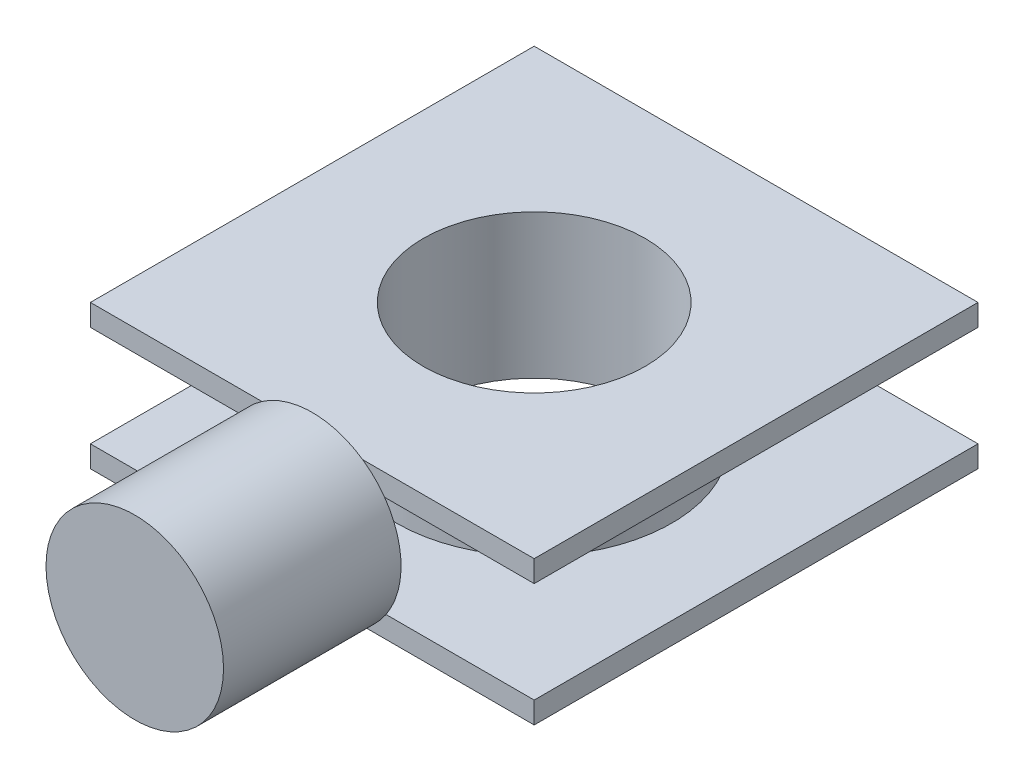
SolidWorks part; units mm, degrees
ref_plane "Front Plane" through (0, 0, 0) normal (0, 0, 1) x (1, 0, 0)
ref_plane "Top Plane" through (0, 0, 0) normal (0, 1, 0) x (1, 0, 0)
ref_plane "Right Plane" through (0, 0, 0) normal (1, 0, 0) x (0, 0, -1)
sketch "Sketch1" plane through (0, 0, 0) normal (0, 1, 0) x (1, 0, 0)
  line L1 (25, -25) -> (-25, -25)
  line L2 (25, -25) -> (25, 25)
  line L3 (25, 25) -> (-25, 25)
  line L4 (-25, -25) -> (-25, 25)
  line L5 (25, -25) -> (-25, 25) construction
  line L6 (25, 25) -> (-25, -25) construction
  circle A1 centre (0, 0) radius 12.5
  circle A2 centre (0, 0) radius 15.5
  circle A3 centre (0, 0) radius 100
  dimension "D2" = 25
  dimension "D3" = 3
  dimension "D4" = 200
  dimension "D5" = 50
  dimension "D6" = 50
extrude "Boss-Extrude1" add sketch "Sketch1" along normal blind 15 contours A2 A1 region at (-15.0616, 0, 0)
sketch "Sketch2" plane through (0, 0, 0) normal (0, 0, 1) x (1, 0, 0)
  line L0 (-15.5, 0) -> (15.5, 0) construction
  line L1 (-50, 2.4358) -> (50, 2.4358)
  line L2 (-50, 2.4358) -> (-50, -2.4358)
  line L3 (-50, -2.4358) -> (50, -2.4358)
  line L4 (50, 2.4358) -> (50, -2.4358)
  line L5 (-50, 2.4358) -> (50, -2.4358) construction
  line L6 (-50, -2.4358) -> (50, 2.4358) construction
  line L7 (-1000, 0) -> (49000, 0) construction
  line L8 (-50, 0) -> (50, 0)
  line L9 (0, -1000) -> (0, 49000) construction
  line L10 (-50, 18.6667) -> (50, 18.6667)
  line L11 (-50, 18.6667) -> (-50, 13.795)
  line L12 (-50, 13.795) -> (50, 13.795)
  line L13 (50, 18.6667) -> (50, 13.795)
  line L14 (-50, 18.6667) -> (50, 13.795) construction
  line L15 (-50, 13.795) -> (50, 18.6667) construction
  line L16 (-50, 16.2308) -> (50, 16.2308)
  point P0 (0, 0)
  point P12 (0, 16.2308)
  point P20 (0, 0)
  dimension "D1" = 100
  dimension "D2" = 100
extrude "Boss-Extrude2" add sketch "Sketch2" along normal blind 50 and the other way blind 50 contours L2 L8 L4 L1 | L16 L11 L12 L13 region at (0, 1.2179, 0) region at (0, 15.0129, 0)
extrude "Cut-Extrude1" cut sketch "Sketch1<4>" along normal blind 20 contours A1 region at (0, 0, 0)
sketch "Sketch1<4>" plane through (0, 0, 0) normal (0, 1, 0) x (1, 0, 0) same geometry as "Sketch1"
extrude "Cut-Extrude2" cut sketch "Sketch1<7>" along normal blind 20 contours A3 region at (-97.1716, 0, 0)
sketch "Sketch1<7>" plane through (0, 0, 0) normal (0, 1, 0) x (1, 0, 0) same geometry as "Sketch1"
sketch "Sketch3" plane through (0, 0, 0) normal (0, 0, 1) x (1, 0, 0)
  line L0 (0, -1000) -> (0, 49000) construction
  circle A0 centre (0, 8.0852) radius 10
  dimension "D1" = 20
sketch "Sketch4" plane through (0, 0, 25) normal (0, 0, 1) x (1, 0, 0)
  line L0 (0, -1000) -> (0, 49000) construction
  line L1 (25, 0) -> (-25, 0) construction
  circle A0 centre (0, 8) radius 10
  point P5 (0, 0)
  point P7 (0, 0)
  point P8 (0, 8.0743)
  dimension "D1" = 20
  dimension "D2" = 8
extrude "Boss-Extrude3" add sketch "Sketch4" along normal blind 20
